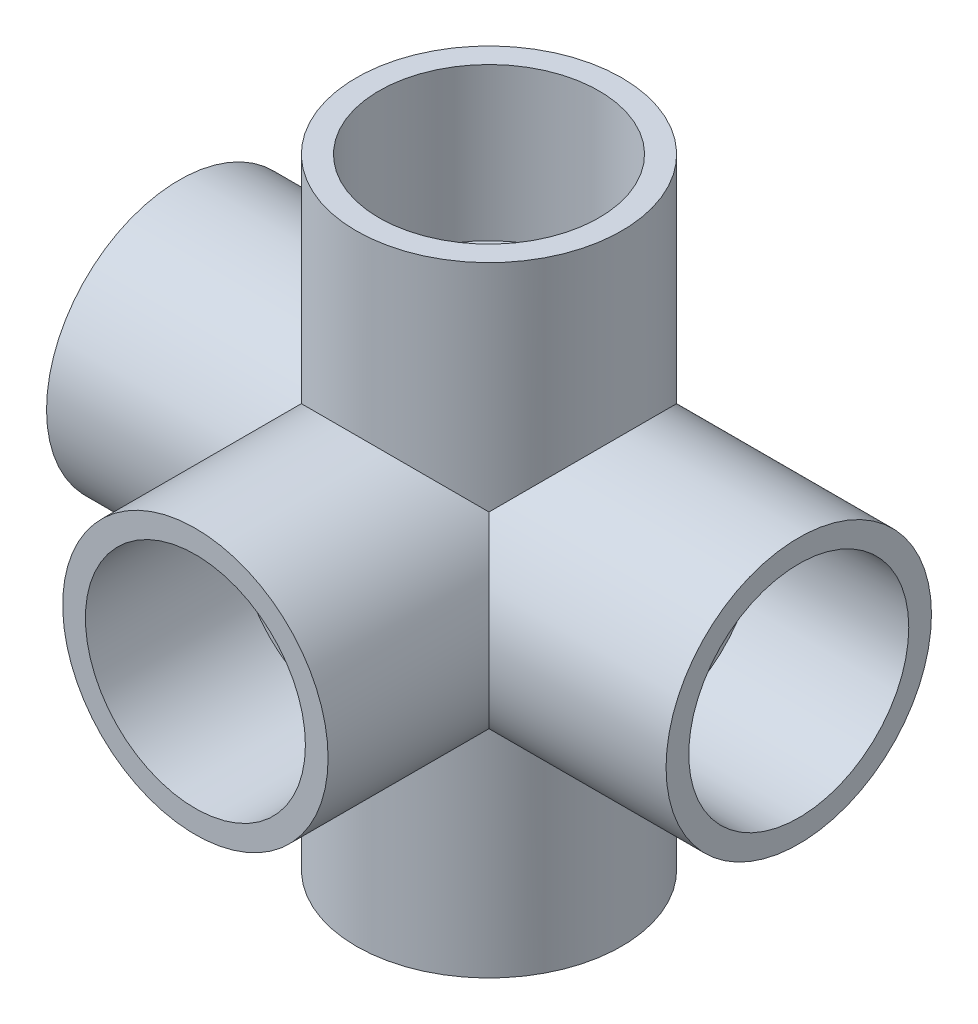
SolidWorks part; units mm, degrees
ref_plane "前视基准面" through (0, 0, 0) normal (0, 0, 1) x (1, 0, 0)
ref_plane "上视基准面" through (0, 0, 0) normal (0, 1, 0) x (1, 0, 0)
ref_plane "右视基准面" through (0, 0, 0) normal (1, 0, 0) x (0, 0, -1)
other "Configuration Table"
sketch "草图1" plane through (0, 0, 0) normal (0, 1, 0) x (1, 0, 0)
  circle A14 centre (0, 0) radius 19.3
  circle A15 centre (0, 0) radius 16
  circle A16 centre (0, 0) radius 13.6
  dimension "D3" = 2.4
  dimension "D1" = 32
  dimension "D2" = 3.3
extrude "凸台-拉伸1" add sketch "草图1" along normal mid plane 90.1 contours A14 | A16
sketch "草图3" plane through (0, 0, 0) normal (1, 0, 0) x (0, 0, -1)
  circle A0 centre (0, 0) radius 19.3
  circle A1 centre (0, 0) radius 16
  circle A2 centre (0, 0) radius 13.6
  dimension "D1" = 3.3
  dimension "D2" = 32
  dimension "D3" = 2.4
extrude "凸台-拉伸3" add sketch "草图3" along normal mid plane 90.1 contours A0 | A2
sketch "草图2" plane through (0, 0, 0) normal (0, 0, 1) x (1, 0, 0)
  circle A0 centre (0, 0) radius 16
  circle A1 centre (0, 0) radius 19.3
  circle A2 centre (0, 0) radius 13.6
  dimension "D1" = 32
  dimension "D2" = 3.3
  dimension "D3" = 2.4
extrude "凸台-拉伸2" add sketch "草图2" along normal blind 42.7 contours A1 | A2
extrude "切除-拉伸1" cut sketch "草图1<13>" against normal through all both and the other way through all contours A16
sketch "草图1<13>" plane through (0, 0, 0) normal (0, 1, 0) x (1, 0, 0) same geometry as "草图1"
extrude "切除-拉伸2" cut sketch "草图3<8>" against normal through all both and the other way through all contours A2
sketch "草图3<8>" plane through (0, 0, 0) normal (1, 0, 0) x (0, 0, -1) same geometry as "草图3"
extrude "切除-拉伸3" cut sketch "草图2<8>" against normal up to next from surface contours A2 starting at face at (19.3, 0, 42.7)
sketch "草图2<8>" plane through (0, 0, 0) normal (0, 0, 1) x (1, 0, 0) same geometry as "草图2"
extrude "切除-拉伸4" cut sketch "草图1<15>" along normal blind 22.2 from surface contours A15 starting at face at (0, -45.05, 19.3)
sketch "草图1<15>" plane through (0, 0, 0) normal (0, 1, 0) x (1, 0, 0) same geometry as "草图1"
extrude "切除-拉伸5" cut sketch "草图1<16>" against normal blind 22.2 from surface contours A15 starting at face at (0, 45.05, 19.3)
sketch "草图1<16>" plane through (0, 0, 0) normal (0, 1, 0) x (1, 0, 0) same geometry as "草图1"
extrude "切除-拉伸6" cut sketch "草图3<9>" along normal blind 22.2 from surface contours A1 starting at face at (-45.05, 0, -19.3)
sketch "草图3<9>" plane through (0, 0, 0) normal (1, 0, 0) x (0, 0, -1) same geometry as "草图3"
extrude "切除-拉伸7" cut sketch "草图3<10>" against normal blind 22.2 from surface contours A1 starting at face at (45.05, 0, -19.3)
sketch "草图3<10>" plane through (0, 0, 0) normal (1, 0, 0) x (0, 0, -1) same geometry as "草图3"
extrude "切除-拉伸8" cut sketch "草图2<9>" against normal blind 22.2 from surface contours A0 starting at face at (19.3, 0, 42.7)
sketch "草图2<9>" plane through (0, 0, 0) normal (0, 0, 1) x (1, 0, 0) same geometry as "草图2"
ref_plane "基准面1" through (0, 0, -19.3) normal (0, 0, -1) x (-1, 0, 0)
